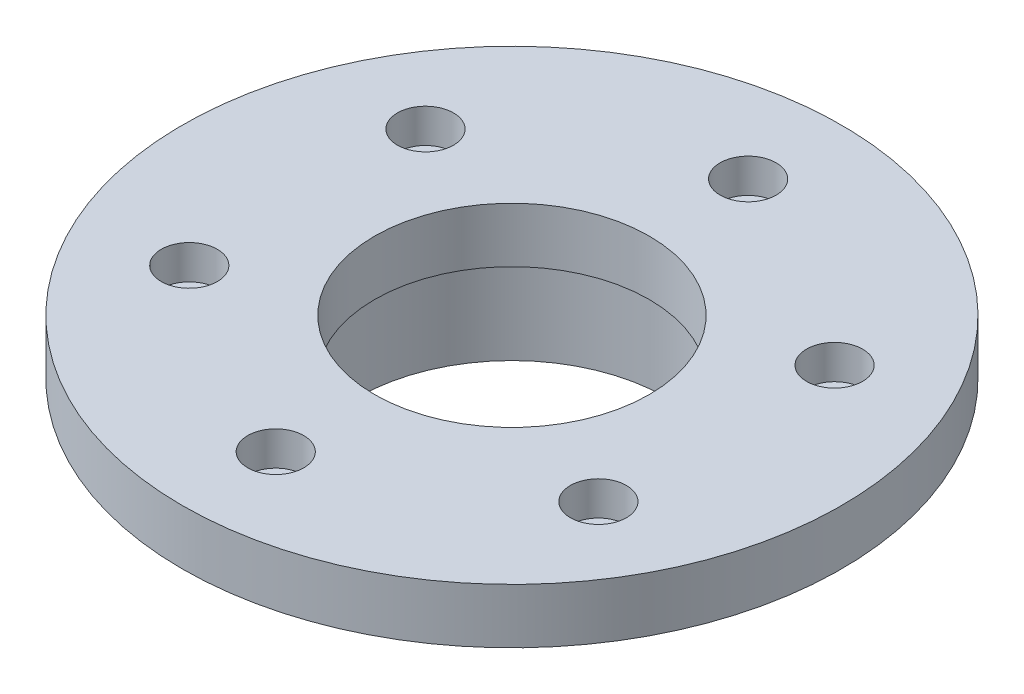
SolidWorks part; units mm, degrees
ref_plane "Front Plane" through (0, 0, 0) normal (0, 0, 1) x (1, 0, 0)
ref_plane "Top Plane" through (0, 0, 0) normal (0, 1, 0) x (1, 0, 0)
ref_plane "Right Plane" through (0, 0, 0) normal (1, 0, 0) x (0, 0, -1)
sketch "Sketch1" plane through (0, 0, 0) normal (0, 1, 0) x (1, 0, 0)
  circle A7 centre (0, 0) radius 30
  point P18 (0, 0)
  dimension "D3" = 60
extrude "Boss-Extrude1" add sketch "Sketch1" along normal blind 5 contours A7
sketch "Sketch2" plane through (0, 5, 0) normal (0, 1, 0) x (1, 0, 0)
  circle A0 centre (0, 0) radius 21.5
  circle A1 centre (0, 21.5) radius 2.55
  circle A2 centre (18.6195, 10.75) radius 2.55
  circle A3 centre (18.6195, -10.75) radius 2.55
  circle A4 centre (0, -21.5) radius 2.55
  circle A5 centre (-18.6195, -10.75) radius 2.55
  circle A6 centre (-18.6195, 10.75) radius 2.55
  point P17 (0, 0)
  dimension "D1" = 43
  dimension "D2" = 5.1
  dimension "D3" = 6
extrude "Cut-Extrude1" cut sketch "Sketch2" against normal blind 3.1 contours A1 | A2 | A3 | A4 | A5 | A6
sketch "Sketch3" plane through (0, 0, 0) normal (0, -1, 0) x (1, 0, 0)
  circle A0 centre (0, 0) radius 14.05
  circle A1 centre (0, 0) radius 16
  dimension "D1" = 28.1
  dimension "D2" = 32
extrude "Boss-Extrude2" add sketch "Sketch3" along normal blind 8.5
sketch "Sketch4" plane through (0, 5, 0) normal (0, 1, 0) x (1, 0, 0)
  circle A0 centre (0, 0) radius 12.5
  dimension "D1" = 25
extrude "Cut-Extrude2" cut sketch "Sketch4" against normal blind 8.5
